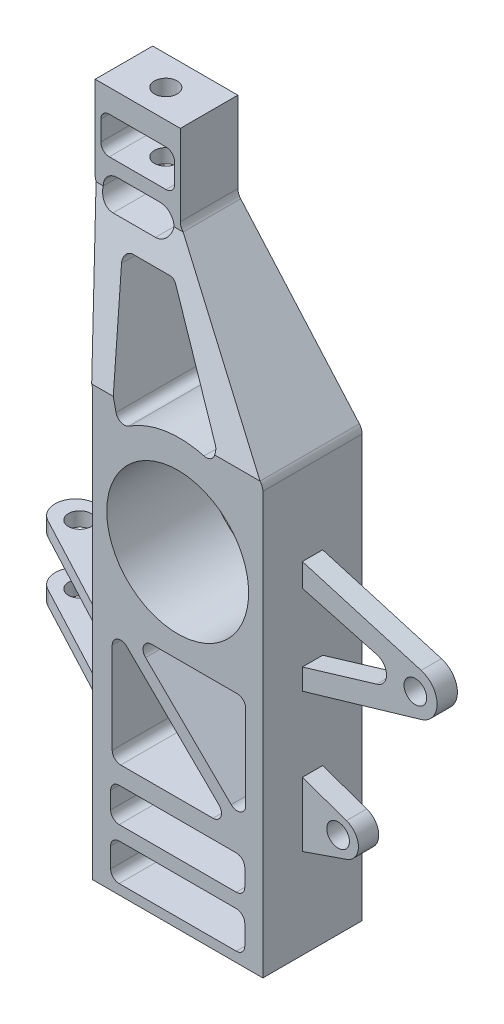
SolidWorks part; units mm, degrees
material "7075-T6 (SN)"
ref_plane "Front Plane" through (0, 0, 0) normal (0, 0, 1) x (1, 0, 0)
ref_plane "Top Plane" through (0, 0, 0) normal (0, 1, 0) x (1, 0, 0)
ref_plane "Right Plane" through (0, 0, 0) normal (1, 0, 0) x (0, 0, -1)
sketch "Sketch1" plane through (0, 0, 0) normal (0, 0, 1) x (1, 0, 0)
  line L3 (30, -10) -> (-30, -10)
  line L4 (0, 0) -> (0, 205)
  line L5 (0, 205) -> (-28.8109, 205) construction
  line L6 (-28.8109, 205) -> (0, 0) construction
  line L7 (30, -10) -> (30, 140)
  line L13 (-30, 140) -> (-30, -10)
  line L15 (-13.8109, 190) -> (-13.8109, 220)
  line L16 (-13.8109, 220) -> (-43.8109, 220)
  line L17 (-43.8109, 220) -> (-43.8109, 190)
  line L19 (-43.8109, 190) -> (-30, 140)
  line L20 (-13.8109, 190) -> (30, 140)
  dimension "D1" = 205
  dimension "D2" = 8
  dimension "D3" = 30
  dimension "D4" = 30
  dimension "D5" = 10
  dimension "D6" = 15
  dimension "D7" = 15
  dimension "D8" = 15
  dimension "D9" = 15
  dimension "D10" = 30
  dimension "D11" = 150
  dimension "D12" = 150
sketch "Sketch3" plane through (0, 0, 0) normal (1, 0, 0) x (0, 0, -1)
  line L0 (0, 205) -> (0, 0) construction
  line L1 (0, 205) -> (0, 0) construction
  line L2 (7.1588, 205) -> (0, 0) construction
  line L3 (0, 205) -> (7.1588, 205)
  dimension "D1" = 2
  dimension "D2" = 205
extrude "Boss-Extrude1" add sketch "Sketch1" along normal mid plane 35 contours L17 L19 L13 L3 L7 L20 L15 L16 region at (-4.5054, 93.3745, 0)
sketch "Sketch4" plane through (0, 0, 0) normal (0, 0, 1) x (1, 0, 0)
  line L0 (0, 205.3073) -> (-28.8541, 205.3073) construction
  line L1 (0, 205) -> (0, 0) construction
  line L2 (-28.8541, 205.3073) -> (0, 0) construction
  dimension "D1" = 8
sketch3d "3DSketch1"
  line L0 (0, 205, -7.1588) -> (-28.8601, 205, -7.1588) construction
  line L1 (-28.8601, 205, -7.1588) -> (-28.8265, 205.111, 0) construction
  line L2 (-28.8541, 205.3073, 0) -> (0, 0, 0) construction
  line L3 (0, 205, 0) -> (0, 205, -7.1588) construction
  line L4 (0, 205, -7.1588) -> (0, 0, 0) construction
  point P12 (-28.8601, 205, -7.1588)
sketch3d "3DSketch2"
  line L0 (-28.8601, 205, -7.1588) -> (0, 0, 0)
sketch "Sketch6" plane through (0, 0, -17.5) normal (0, 0, -1) x (-1, 0, 0)
  line L0 (16.0353, 193.8847) -> (40.9774, 193.8847)
  line L1 (23.6291, 6.5) -> (-23.6291, 6.5)
  line L2 (23.6291, 6.5) -> (23.6291, -6.5)
  line L3 (23.6291, -6.5) -> (-23.6291, -6.5)
  line L4 (-23.6291, 6.5) -> (-23.6291, -6.5)
  line L5 (23.6291, 6.5) -> (-23.6291, -6.5) construction
  line L6 (23.6291, -6.5) -> (-23.6291, 6.5) construction
  line L7 (23.6291, 23.5) -> (-23.6291, 23.5)
  line L8 (23.6291, 23.5) -> (23.6291, 11.5)
  line L9 (23.6291, 11.5) -> (-23.6291, 11.5)
  line L10 (-23.6291, 23.5) -> (-23.6291, 11.5)
  line L11 (23.6291, 23.5) -> (-23.6291, 11.5) construction
  line L12 (23.6291, 11.5) -> (-23.6291, 23.5) construction
  line L13 (41.8541, 211.8073) -> (15.8541, 211.8073)
  line L14 (41.8541, 211.8073) -> (41.8541, 198.8073)
  line L15 (41.8541, 198.8073) -> (15.8541, 198.8073)
  line L16 (15.8541, 211.8073) -> (15.8541, 198.8073)
  line L17 (41.8541, 211.8073) -> (15.8541, 198.8073) construction
  line L18 (41.8541, 198.8073) -> (15.8541, 211.8073) construction
  line L19 (40.9774, 193.8847) -> (40.9774, 183.8847)
  line L20 (40.9774, 183.8847) -> (16.0353, 183.8847)
  line L21 (16.0353, 183.8847) -> (16.0353, 193.8847)
  point P0 (0, 0)
  point P6 (0, 17.5)
  point P11 (28.8541, 205.3073)
  dimension "D1" = 13
  dimension "D2" = 12
  dimension "D3" = 5
  dimension "D4" = 13
  dimension "D5" = 10
  dimension "D6" = 5
  dimension "D7" = 26
  dimension "D8" = 24.942
extrude "Cut-Extrude1" cut sketch "Sketch6" against normal through all
sketch "Sketch7" plane through (0, 0, -17.5) normal (0, 0, -1) x (-1, 0, 0)
  line L0 (0, 205) -> (0, 0) construction
  line L1 (-30, -10) -> (30, -10) construction
  circle A0 centre (0, 105) radius 25
  point P0 (0, 105)
  dimension "D2" = 50
  dimension "D1" = 115
extrude "Cut-Extrude2" cut sketch "Sketch7" against normal through all
sketch "Sketch8" plane through (0, 220, 0) normal (0, 1, 0) x (1, 0, 0)
  circle A0 centre (-28.8601, 7.1588) radius 4
  dimension "D1" = 8
extrude "Cut-Extrude3" cut sketch "Sketch8" against normal blind 30
sketch "Sketch10" plane through (0, -10, 0) normal (0, -1, 0) x (1, 0, 0)
  circle A0 centre (0, 0) radius 4
  dimension "D1" = 8
extrude "Cut-Extrude4" cut sketch "Sketch10" against normal blind 30
sketch "Sketch11" plane through (30, 0, 0) normal (1, 0, 0) x (0, 0, -1)
  line L1 (-3.5809, 110.12) -> (3.5794, 110.12)
  line L2 (-3.5809, 110.12) -> (-3.5809, 70.5679)
  line L3 (-3.5809, 70.5679) -> (3.5794, 70.5679)
  line L4 (3.5794, 110.12) -> (3.5794, 70.5679)
  line L5 (-3.5809, 44.2881) -> (3.5794, 44.2881)
  line L6 (-3.5809, 44.2881) -> (-3.5809, 21.6508)
  line L7 (-3.5809, 21.6508) -> (3.5794, 21.6508)
  line L8 (3.5794, 44.2881) -> (3.5794, 21.6508)
extrude "Boss-Extrude2" add sketch "Sketch11" along normal blind 50
sketch "Sketch12" plane through (0, 0, 3.5809) normal (0, 0, 1) x (1, 0, 0)
  line L0 (30, 90.3439) -> (80, 90.3439) construction
  line L1 (30, 110.12) -> (30, 70.5679) construction
  line L2 (80, 110.12) -> (80, 70.5679) construction
  line L3 (30, 32.9695) -> (80, 32.9695) construction
  line L4 (30, 44.2881) -> (30, 21.6508) construction
  line L5 (80, 44.2881) -> (80, 21.6508) construction
sketch "Sketch13" plane through (0, 0, 3.5809) normal (0, 0, 1) x (1, 0, 0)
  line L0 (30, 90.3439) -> (80, 90.3439) construction
  line L1 (30, 32.9695) -> (80, 32.9695) construction
  circle A0 centre (69.8025, 90.3439) radius 4
  circle A1 centre (42.5917, 32.9695) radius 4
  dimension "D1" = 8
  dimension "D2" = 8
  dimension "D3" = 63.5
extrude "Cut-Extrude5" cut sketch "Sketch13" against normal blind 50
sketch "Sketch14" plane through (0, 0, 3.5809) normal (0, 0, 1) x (1, 0, 0)
  line L0 (30, 110.12) -> (71.8574, 97.8439)
  line L1 (30, 110.12) -> (80, 110.12)
  line L2 (71.8574, 82.8439) -> (30, 70.5679)
  line L3 (80, 110.12) -> (80, 70.5679)
  line L4 (80, 70.5679) -> (30, 70.5679)
  circle A0 centre (69.8025, 90.3439) radius 4 construction
  arc A1 (71.8574, 97.8439) -> (71.8574, 82.8439) centre (69.6578, 90.3439) cw
  dimension "D1" = 7.5
  dimension "D2" = 7.5
extrude "Cut-Extrude6" cut sketch "Sketch14" against normal blind 50
sketch "Sketch15" plane through (0, 0, 3.5809) normal (0, 0, 1) x (1, 0, 0)
  line L1 (30, 44.2881) -> (80, 44.2881)
  line L3 (80, 44.2881) -> (80, 21.6508)
  line L4 (80, 21.6508) -> (30, 21.6508)
  line L5 (30, 44.2881) -> (45.5568, 38.8498)
  line L7 (45.5365, 27.0226) -> (30, 21.6508)
  arc A2 (45.5568, 38.8498) -> (45.5365, 27.0226) centre (43.4907, 32.9397) cw
extrude "Cut-Extrude7" cut sketch "Sketch15" against normal blind 50
sketch3d "3DSketch3"
  point P0 (-85, 34, -33)
sketch "Sketch18" plane through (-30, 0, 0) normal (-1, 0, 0) x (0, 0, 1)
  line L0 (-33, 34) -> (22.4569, 34) construction
  line L1 (0, 205) -> (0, 0) construction
  line L2 (11.6727, 47) -> (-11.6727, 47)
  line L3 (11.6727, 47) -> (11.6727, 42)
  line L4 (11.6727, 42) -> (-11.6727, 42)
  line L6 (11.6727, 47) -> (-11.6727, 42) construction
  line L7 (11.6727, 42) -> (-11.6727, 47) construction
  line L8 (-11.6727, 26) -> (-45.213, 26)
  line L9 (11.6727, 26) -> (-11.6727, 26)
  line L10 (11.6727, 26) -> (11.6727, 21)
  line L11 (11.6727, 21) -> (-11.6727, 21)
  line L13 (11.6727, 26) -> (-11.6727, 21) construction
  line L14 (11.6727, 21) -> (-11.6727, 26) construction
  line L15 (-45.213, 26) -> (-45.213, 21)
  line L16 (-45.213, 21) -> (-11.6727, 21)
  line L17 (-11.6727, 47) -> (-45.5276, 47)
  line L18 (-45.5276, 47) -> (-45.5276, 42)
  line L19 (-45.5276, 42) -> (-11.6727, 42)
  point P3 (0, 44.5)
  point P10 (0, 23.5)
  dimension "D1" = 8
  dimension "D2" = 8
  dimension "D3" = 5
  dimension "D4" = 5
extrude "Boss-Extrude3" add sketch "Sketch18" along normal blind 70
sketch "Sketch19" plane through (0, 47, 0) normal (0, 1, 0) x (1, 0, 0)
  circle A0 centre (-85, 33) radius 4
  dimension "D1" = 8
extrude "Cut-Extrude8" cut sketch "Sketch19" against normal blind 70
sketch "Sketch20" plane through (0, 21, 0) normal (0, -1, 0) x (1, 0, 0)
  line L0 (-78.7742, -45.213) -> (-78.7742, -11.3955)
  line L1 (-100, -45.213) -> (-30, -45.213) construction
  line L2 (-78.7742, -11.3955) -> (-30, -11.3955)
  line L3 (-30, -17.5) -> (-30, 11.6727) construction
  line L4 (-30, -11.3955) -> (-30, -45.213)
  line L5 (-30, -45.213) -> (-78.7742, -45.213)
extrude "Cut-Extrude9" [suppressed] cut sketch "Sketch20" against normal blind 70
sketch "Sketch22" [suppressed] plane through (0, 21, 0) normal (0, -1, 0) x (1, 0, 0)
  line L0 (-91.2054, -38.9523) -> (-91.2054, 1.0345)
  line L1 (-100, -38.9523) -> (-78.7742, -38.9523) construction
  line L2 (-91.2054, 1.0345) -> (-30, 1.0345)
  line L3 (-30, 17.5) -> (-30, -17.5) construction
  line L4 (-91.2054, -38.9523) -> (-100, -38.9523)
  line L5 (-100, -38.9523) -> (-100, 11.6727)
  line L6 (-100, 11.6727) -> (-30, 11.6727)
  line L7 (-30, 11.6727) -> (-30, 1.0345)
  dimension "D1" = 12.43
extrude "Cut-Extrude10" [suppressed] cut sketch "Sketch22" against normal blind 70
fillet "Fillet1" [suppressed] radius 5
fillet "Fillet2" [suppressed] radius 5
fillet "Fillet3" [suppressed] radius 5
fillet "Fillet4" radius 5 4 edges at (-40.9774, 183.8847, 0) (-16.0353, 183.8847, 0) (-16.0353, 193.8847, 0) (-40.9774, 193.8847, 0)
sketch "Sketch24" plane through (0, 0, 17.5) normal (0, 0, 1) x (1, 0, 0)
  line L0 (-23.0801, 29.9624) -> (-23.0801, 72.2433)
  line L1 (-23.0801, 72.2433) -> (19.739, 29.9624)
  line L2 (19.739, 29.9624) -> (-23.0801, 29.9624)
  line L3 (-16.5172, 72.2433) -> (23.9546, 72.2433)
  line L4 (23.9546, 72.2433) -> (23.9546, 32.2802)
  line L5 (23.9546, 32.2802) -> (-16.5172, 72.2433)
extrude "Cut-Extrude11" cut sketch "Sketch24" against normal through all
fillet "Fillet5" radius 3 2 edges at (23.9546, 72.2433, 0) (-16.5172, 72.2433, 0)
fillet "Fillet6" radius 3 4 edges at (19.739, 29.9624, 0) (-23.0801, 29.9624, 0) (-23.0801, 72.2433, 0) (23.9546, 32.2802, 0)
sketch "Sketch25" plane through (0, 0, 17.5) normal (0, 0, 1) x (1, 0, 0)
  line L4 (19.6263, 134.005) -> (-12.2895, 176.9221)
  line L6 (-20.752, 132.1204) -> (-30.5031, 176.9221)
  line L7 (-30.5031, 176.9221) -> (-12.2895, 176.9221)
  arc A0 (-20.752, 132.1204) -> (19.6263, 134.005) centre (0.631, 107.4855) cw
extrude "Cut-Extrude12" cut sketch "Sketch25" against normal through all
fillet "Fillet9" radius 3 4 edges at (19.6263, 134.005, 0) (-20.752, 132.1204, 0) (-12.2895, 176.9221, 0) (-30.5031, 176.9221, 0)
sketch "Sketch26" plane through (0, 0, 3.5809) normal (0, 0, 1) x (1, 0, 0)
  line L0 (30, 101.9532) -> (56.1856, 94.8778)
  line L1 (30, 110.12) -> (30, 70.5679) construction
  line L3 (56.1856, 85.8135) -> (30, 77.9528)
  line L4 (30, -10) -> (30, 140) construction
  line L5 (30, 110.12) -> (71.8574, 97.8439) construction
  line L6 (71.8574, 82.8439) -> (30, 70.5679) construction
  line L7 (30, 101.9532) -> (30, 77.9528)
  arc A0 (56.1856, 94.8778) -> (56.1856, 85.8135) centre (54.961, 90.3456) cw
  dimension "D1" = 7.2567
  dimension "D2" = 7.26
extrude "Cut-Extrude13" cut sketch "Sketch26" against normal through all
fillet "Fillet10" radius 3 12 edges at (-23.6291, -6.5, 0) (-23.6291, 6.5, 0) (23.6291, -6.5, 0) (23.6291, 6.5, 0) (23.6291, 23.5, 0) (-23.6291, 23.5, 0) (23.6291, 11.5, 0) (-23.6291, 11.5, 0) (-15.8541, 198.8073, 0) (-41.8541, 198.8073, 0) (-41.8541, 211.8073, 0) (-15.8541, 211.8073, 0)
sketch3d "3DSketch4"
  line L0 (0, 0, 0) -> (0, 205.3073, 0) construction
  line L1 (0, 205.3073, 0) -> (-28.8265, 205.111, 0) construction
  line L2 (-28.8265, 205.111, 0) -> (-28.8601, 205, -7.1588) construction
  line L3 (-28.8601, 205, -7.1588) -> (0, 0, 0) construction
  line L4 (-28.8601, 205, -7.1588) -> (0, 0, 0)
  point P8 (0, 0, 0)
  point P9 (0, 0, 0)
sketch "Sketch29" plane through (0, 21, 0) normal (0, -1, 0) x (1, 0, 0)
  line L0 (-30, 4.8555) -> (-90.4698, -27.2177)
  line L2 (-83.6857, -40.013) -> (-30, -11.5592)
  line L3 (-30, -17.5) -> (-30, 11.6727) construction
  line L4 (-30, 11.6727) -> (-100, 11.6727)
  line L5 (-100, 11.6727) -> (-100, -45.5276)
  line L6 (-100, -45.5276) -> (-30, -45.5276)
  line L7 (-30, -45.5276) -> (-30, -11.5592)
  line L10 (-30, 11.6727) -> (-30, 4.8555)
  arc A0 (-90.4698, -27.2177) -> (-83.6857, -40.013) centre (-87.0768, -33.6148) ccw
extrude "Cut-Extrude14" cut sketch "Sketch29" against normal blind 50
fillet "Fillet11" radius 4 4 edges at (30, 140, 0) (-30, 140, 0) (-43.8109, 190, 0) (-13.8109, 190, 0)
sketch "Sketch31" plane through (30, 0, 0) normal (1, 0, 0) x (0, 0, -1)
  line L0 (-17.5, 141.1316) -> (-2.7648, 188.8684)
  line L1 (17.5, 188.8684) -> (-17.5, 188.8684) construction
  line L2 (-2.7648, 188.8684) -> (-2.7648, 220)
  line L3 (-17.5, 220) -> (17.5, 220) construction
  line L4 (-2.7648, 220) -> (-17.5, 220)
  line L5 (-17.5, 220) -> (-17.5, 141.1316)
extrude "Cut-Extrude16" cut sketch "Sketch31" against normal blind 100
